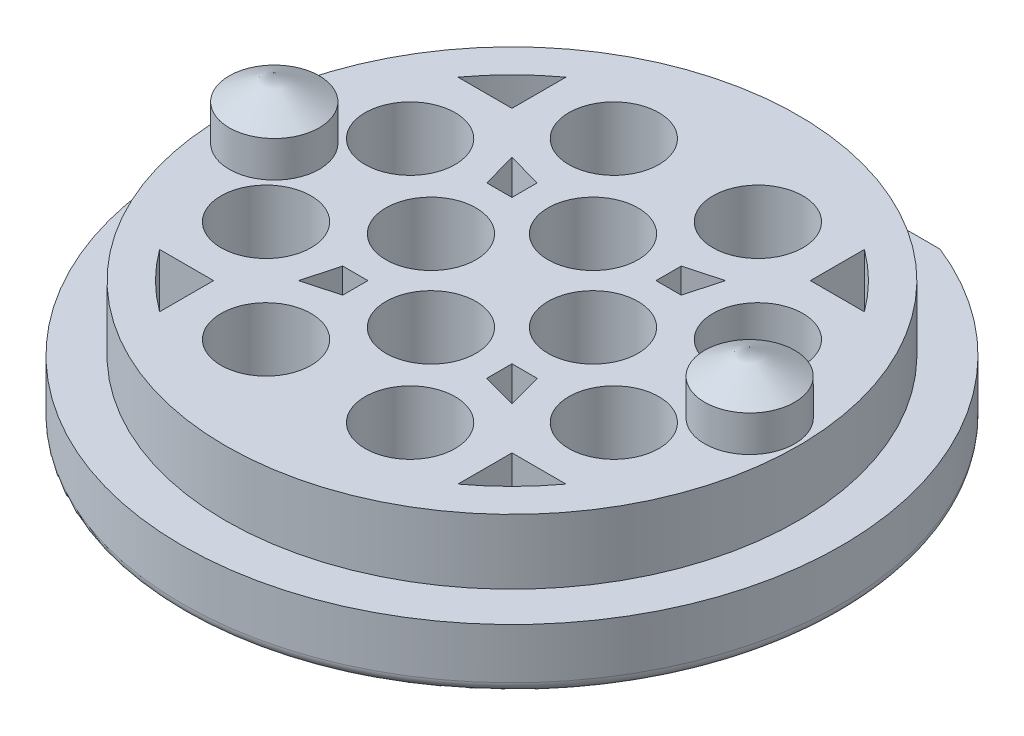
SolidWorks part; units mm, degrees
ref_plane "Front Plane" through (0, 0, 0) normal (0, 0, 1) x (1, 0, 0)
ref_plane "Top Plane" through (0, 0, 0) normal (0, 1, 0) x (1, 0, 0)
ref_plane "Right Plane" through (0, 0, 0) normal (1, 0, 0) x (0, 0, -1)
sketch "Sketch1" plane through (0, 0, 0) normal (0, 1, 0) x (1, 0, 0)
  circle A0 centre (0, 0) radius 9.15
  dimension "D1" = 18.3
extrude "Boss-Extrude1" add sketch "Sketch1" along normal blind 1.4 and the other way blind 0.3
sketch "Sketch2" plane through (0, 0, 0) normal (0, 1, 0) x (1, 0, 0)
  circle A0 centre (0, 0) radius 8.25
  dimension "D1" = 16.5
extrude "Cut-Extrude1" cut sketch "Sketch2" against normal blind 14
sketch "Sketch3" plane through (0, 1.4, 0) normal (0, 1, 0) x (1, 0, 0)
  circle A0 centre (0, 0) radius 7.95
  dimension "D1" = 15.9
extrude "Boss-Extrude2" add sketch "Sketch3" along normal blind 1.8
sketch "Sketch4" plane through (0, 3.2, 0) normal (0, 1, 0) x (1, 0, 0)
  line L0 (-7.95, 0) -> (7.95, 0) construction
  line L1 (0, 7.95) -> (0, -7.95) construction
  line L2 (-4.8284, 2) -> (-2, 4.8284) construction
  line L3 (0, 0) -> (-4.9497, 4.9497) construction
  line L4 (-5.6426, 4.1426) -> (-4.1426, 4.1426)
  line L5 (-4.1426, 5.6426) -> (-4.1426, 4.1426)
  line L6 (-2.7, 2) -> (-2, 2)
  line L7 (-2, 2) -> (-2, 2.7)
  line L8 (-2, 2.7) -> (-2.9644, 2.9644)
  line L9 (-2.9644, 2.9644) -> (-2.7, 2)
  line L10 (0, 0) -> (4.9497, 4.9497) construction
  line L11 (4.8284, 2) -> (2, 4.8284) construction
  line L12 (2.9644, 2.9644) -> (2.7, 2)
  line L13 (2, 2.7) -> (2.9644, 2.9644)
  line L14 (2, 2) -> (2, 2.7)
  line L15 (2.7, 2) -> (2, 2)
  line L16 (4.1426, 5.6426) -> (4.1426, 4.1426)
  line L17 (5.6426, 4.1426) -> (4.1426, 4.1426)
  line L18 (4.8284, -2) -> (2, -4.8284) construction
  line L19 (0, 0) -> (4.9497, -4.9497) construction
  line L20 (0, 0) -> (-4.9497, -4.9497) construction
  line L21 (-4.8284, -2) -> (-2, -4.8284) construction
  line L22 (5.6426, -4.1426) -> (4.1426, -4.1426)
  line L23 (4.1426, -5.6426) -> (4.1426, -4.1426)
  line L24 (2.7, -2) -> (2, -2)
  line L25 (2, -2) -> (2, -2.7)
  line L26 (2, -2.7) -> (2.9644, -2.9644)
  line L27 (2.9644, -2.9644) -> (2.7, -2)
  line L28 (-2.9644, -2.9644) -> (-2.7, -2)
  line L29 (-2, -2.7) -> (-2.9644, -2.9644)
  line L30 (-2, -2) -> (-2, -2.7)
  line L31 (-2.7, -2) -> (-2, -2)
  line L32 (-4.1426, -5.6426) -> (-4.1426, -4.1426)
  line L33 (-5.6426, -4.1426) -> (-4.1426, -4.1426)
  circle A0 centre (0, 0) radius 7.95 construction
  circle A1 centre (0, 0) radius 7.95 construction
  circle A2 centre (-2.25, 0) radius 1.25
  circle A3 centre (0, 2.25) radius 1.25
  circle A4 centre (-2, 4.8284) radius 1.25
  circle A5 centre (-4.8284, 2) radius 1.25
  arc A6 (-4.1426, 5.6426) -> (-5.6426, 4.1426) centre (0, 0) ccw
  arc A7 (4.1426, 5.6426) -> (5.6426, 4.1426) centre (0, 0) cw
  circle A8 centre (4.8284, 2) radius 1.25
  circle A9 centre (2, 4.8284) radius 1.25
  circle A10 centre (2.25, 0) radius 1.25
  circle A11 centre (2, -4.8284) radius 1.25
  circle A12 centre (4.8284, -2) radius 1.25
  arc A13 (4.1426, -5.6426) -> (5.6426, -4.1426) centre (0, 0) ccw
  arc A14 (-4.1426, -5.6426) -> (-5.6426, -4.1426) centre (0, 0) cw
  circle A15 centre (-4.8284, -2) radius 1.25
  circle A16 centre (-2, -4.8284) radius 1.25
  circle A17 centre (0, -2.25) radius 1.25
  point P8 (0, 0)
  point P12 (0, 0)
  dimension "D1" = 2.5
  dimension "D2" = 2.25
  dimension "D3" = 2.25
  dimension "D4" = 2
  dimension "D5" = 2
  dimension "D8" = 7
  dimension "D6" = 4
  dimension "D7" = 45
  dimension "D9" = 45
  dimension "D10" = 1.5
  dimension "D11" = 0.7
  dimension "D12" = 0.7
  dimension "D13" = 1
extrude "Cut-Extrude2" cut sketch "Sketch4" against normal through all
sketch "Sketch6" plane through (0, 3.2, 0) normal (0, 1, 0) x (1, 0, 0)
  line L0 (-6.6, 0) -> (0, 0) construction
  line L1 (0, 0) -> (6.6, 0) construction
  circle A0 centre (-6.6, 0) radius 1.25
  circle A1 centre (6.6, 0) radius 1.25
  dimension "D2" = 2.5
  dimension "D3" = 13.2
  dimension "D4" = 6.6
extrude "Boss-Extrude3" add sketch "Sketch6" along normal blind 1
sketch "Sketch7" plane through (0, 0, 0) normal (0, 0, 1) x (1, 0, 0)
  line L0 (-7.85, 4.2) -> (-6.6, 4.2)
  line L1 (-5.35, 4.2) -> (-7.85, 4.2) construction
  line L2 (-6.6, 4.2) -> (-6.6, 4.9) construction
  line L3 (-6.6, 4.9) -> (-7.85, 4.2)
  line L4 (-6.6, 4.2) -> (-6.6, 4.9)
  dimension "D1" = 0.7
revolve "Revolve1" add sketch "Sketch7" angle 360 about L2
sketch "Sketch8" plane through (0, 0, 0) normal (0, 0, 1) x (1, 0, 0)
  line L0 (7.85, 4.2) -> (6.6, 4.2)
  line L1 (7.85, 4.2) -> (5.35, 4.2) construction
  line L2 (6.6, 4.2) -> (6.6, 4.9) construction
  line L3 (6.6, 4.9) -> (7.85, 4.2)
  line L4 (6.6, 4.2) -> (6.6, 4.9)
  dimension "D1" = 0.7
revolve "Revolve2" add sketch "Sketch8" angle 360 about L2
fillet "Fillet1" radius 0.3 1 edges at (0, -0.3, 9.15)
sketch "Sketch9" plane through (0, 0, 0) normal (0, 1, 0) x (1, 0, 0)
  line L1 (-5.7292, 11.1775) -> (5.7292, 11.1775)
  line L2 (-5.7292, 11.1775) -> (-5.7292, 8.5)
  line L3 (-5.7292, 8.5) -> (5.7292, 8.5)
  line L4 (5.7292, 11.1775) -> (5.7292, 8.5)
  point P4 (0, 8.5)
  dimension "D1" = 8.5
extrude "Cut-Extrude6" cut sketch "Sketch9" along normal blind 2 from offset 0.7
sketch "Croquis1" plane through (0, 0, 0) normal (0, -1, 0) x (1, 0, 0)
  circle A0 centre (0, 0) radius 8.25
extrude "Saliente-Extruir1" add sketch "Croquis1" along normal blind 0.1
